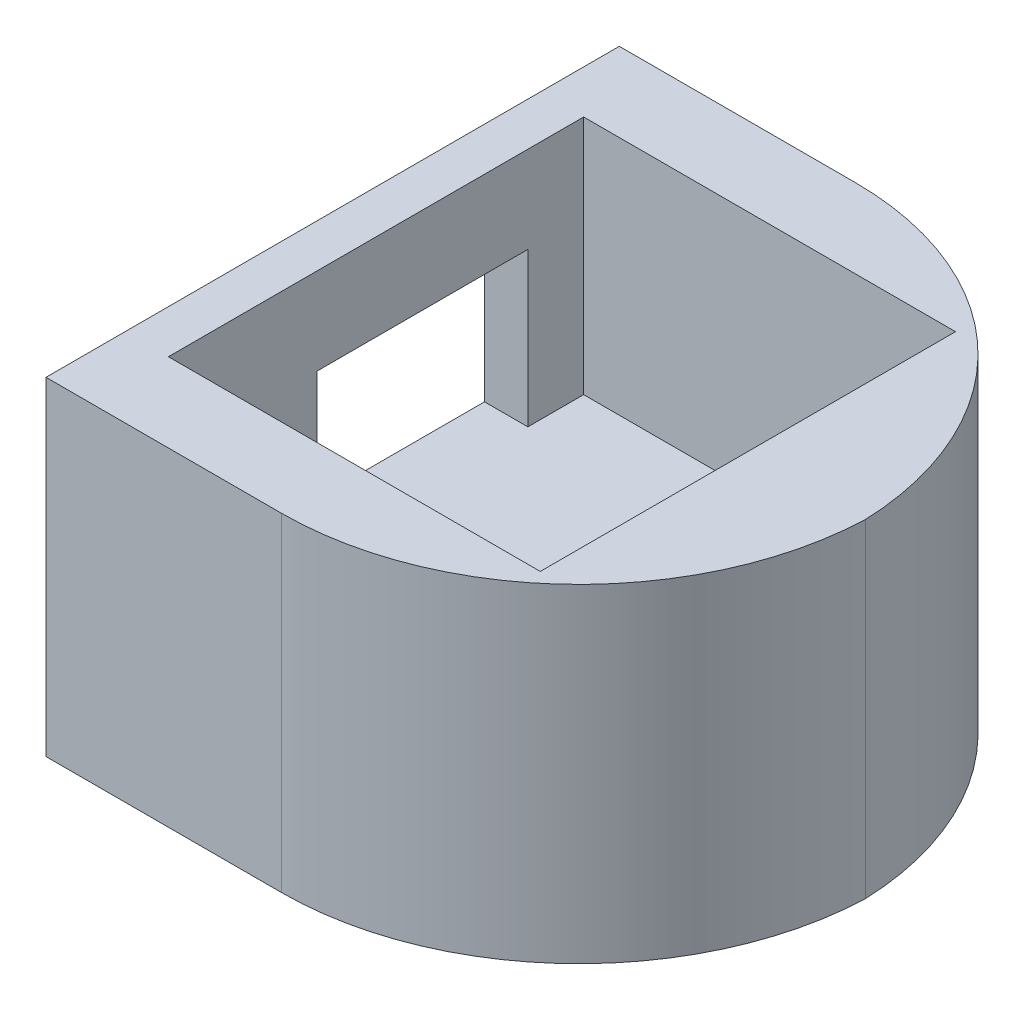
SolidWorks part; units mm, degrees
ref_plane "Front Plane" through (0, 0, 0) normal (0, 0, 1) x (1, 0, 0)
ref_plane "Top Plane" through (0, 0, 0) normal (0, 1, 0) x (1, 0, 0)
ref_plane "Right Plane" through (0, 0, 0) normal (1, 0, 0) x (0, 0, -1)
sketch "Sketch1" plane through (0, 0, 0) normal (0, 1, 0) x (1, 0, 0)
  line L0 (0, 0) -> (0, 46.25)
  line L1 (0, 46.25) -> (43, 46.25)
  line L2 (43, 46.25) -> (43, 0)
  line L3 (43, 0) -> (0, 0)
  dimension "D1" = 43
  dimension "D2" = 46.25
extrude "Boss-Extrude1" add sketch "Sketch1" along normal blind 26.5
fillet "Fillet1" radius 24 2 edges at (43, 13.25, 0) (43, 13.25, -46.25)
sketch "Sketch2" plane through (0, 26.5, 0) normal (0, 1, 0) x (1, 0, 0)
  line L0 (3.5, 6.375) -> (3.5, 39.875)
  line L1 (3.5, 39.875) -> (33.5, 39.875)
  line L2 (33.5, 39.875) -> (33.5, 6.375)
  line L3 (33.5, 6.375) -> (3.5, 6.375)
  line L4 (3.5, 39.875) -> (3.5, 46.25) construction
  line L5 (19, 46.25) -> (0, 46.25) construction
  line L6 (3.5, 6.375) -> (3.5, 0) construction
  line L7 (0, 0) -> (19, 0) construction
  line L8 (0, 46.25) -> (0, 0) construction
  dimension "D1" = 30
  dimension "D2" = 33.5
  dimension "D3" = 3.5
extrude "Cut-Extrude1" cut sketch "Sketch2" against normal blind 19.4
sketch "Sketch4" plane through (3.5, 0, 0) normal (1, 0, 0) x (0, 0, -1)
  line L0 (18.375, 7.1) -> (18.375, 19.5)
  line L1 (39.875, 7.1) -> (6.375, 7.1) construction
  line L2 (18.375, 19.5) -> (35.375, 19.5)
  line L3 (35.375, 19.5) -> (35.375, 7.1)
  line L4 (35.375, 7.1) -> (18.375, 7.1)
  line L5 (39.875, 7.1) -> (39.875, 26.5) construction
  line L6 (6.375, 7.1) -> (6.375, 26.5) construction
  line L7 (39.875, 26.5) -> (6.375, 26.5) construction
  point P10 (26.875, 19.5)
  dimension "D1" = 4.5
  dimension "D2" = 12
  dimension "D3" = 7
extrude "Cut-Extrude2" cut sketch "Sketch4" against normal blind 20
